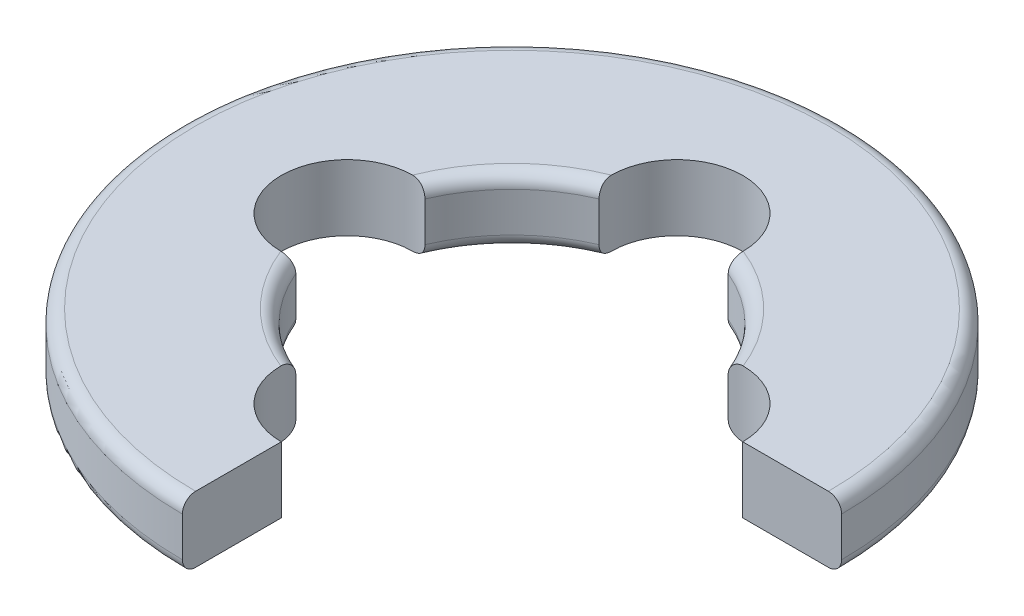
SolidWorks part; units mm, degrees
material "Custom Carbon Steel"
ref_plane "Front Plane" through (0, 0, 0) normal (0, 0, 1) x (1, 0, 0)
ref_plane "Top Plane" through (0, 0, 0) normal (0, 1, 0) x (1, 0, 0)
ref_plane "Right Plane" through (0, 0, 0) normal (1, 0, 0) x (0, 0, -1)
sketch "Sketch1" plane through (0, 0, 0) normal (0, 1, 0) x (1, 0, 0)
  line L0 (0, 0) -> (0, -1.25) construction
  line L1 (0, 0) -> (1.25, 0) construction
  line L2 (0, -1.75) -> (0, -2.5)
  line L3 (1.75, 0) -> (2.5, 0)
  arc A0 (1.15, 0.4899) -> (0.4899, 1.15) centre (0, 0) ccw
  arc A1 (2.5, 0) -> (0, -2.5) centre (0, 0) ccw
  arc A2 (-1.15, 0.4899) -> (-1.15, -0.4899) centre (-1.25, 0) ccw
  arc A3 (0.4899, 1.15) -> (-0.4899, 1.15) centre (0, 1.25) ccw
  arc A4 (1.75, 0) -> (1.15, 0.4899) centre (1.25, 0) ccw
  arc A5 (-0.4899, -1.15) -> (0, -1.75) centre (0, -1.25) ccw
  arc A6 (-0.4899, 1.15) -> (-1.15, 0.4899) centre (0, 0) ccw
  arc A7 (-1.15, -0.4899) -> (-0.4899, -1.15) centre (0, 0) ccw
  dimension "D1" = 2.5
  dimension "D2" = 5
  dimension "D3" = 1
extrude "Boss-Extrude1" add sketch "Sketch1" along normal blind 0.25 and the other way blind 0.25
fillet "Fillet1" radius 0.1 8 edges at (0.8839, -0.25, -0.8839) (-0.8839, -0.25, -0.8839) (-0.8839, -0.25, 0.8839) (-1.7678, -0.25, -1.7678) (0.8839, 0.25, -0.8839) (-0.8839, 0.25, -0.8839) (-0.8839, 0.25, 0.8839) (-1.7678, 0.25, -1.7678)
